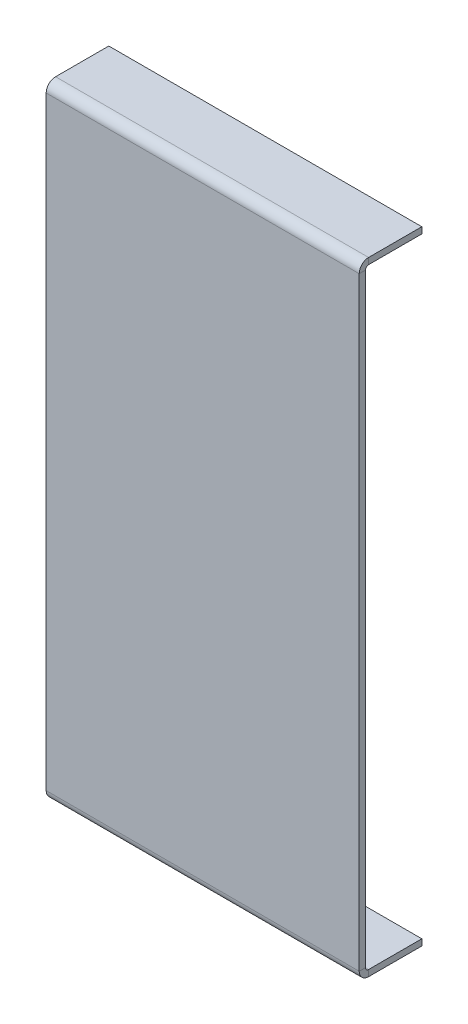
SolidWorks part; units mm, degrees
note: The reader was unsure of these and kept them because the rebuilt part matched: flange length of "边线-法兰1".
ref_plane "前视基准面" through (0, 0, 0) normal (0, 0, 1) x (1, 0, 0)
ref_plane "上视基准面" through (0, 0, 0) normal (0, 1, 0) x (1, 0, 0)
ref_plane "右视基准面" through (0, 0, 0) normal (1, 0, 0) x (0, 0, -1)
sketch "草图1" plane through (0, 0, 0) normal (0, 0, 1) x (1, 0, 0)
  line L1 (-50, 99.5) -> (50, 99.5)
  line L2 (-50, 99.5) -> (-50, -99.5)
  line L3 (-50, -99.5) -> (50, -99.5)
  line L4 (50, 99.5) -> (50, -99.5)
  line L5 (-50, 99.5) -> (50, -99.5) construction
  line L6 (-50, -99.5) -> (50, 99.5) construction
  point P0 (0, 0)
  dimension "D1" = 100
  dimension "D2" = 199
base flange "基体-法兰1" sketch "草图1" thickness 2 reverse thickness direction no parameters "D1"=1
edge flange "边线-法兰1" sketch "草图10" flange profiles "草图10", "草图11" flange angle 90 flange length 20 flange position material inside bend radius 1 thickness 2 relief rectangular parameters "D6"=10, "D8"=1
sketch "草图10" plane through (0, 99.5, -2) normal (0, -1, 0) x (-1, 0, 0)
  line L1 (50, 0) -> (-50, 0) construction
  line L2 (-50, 0) -> (-50, 18)
  line L3 (-50, 18) -> (50, 18)
  line L4 (50, 18) -> (50, 0)
  line L5 (50, 0) -> (-50, 0)
sketch "草图11" plane through (0, -99.5, -2) normal (0, 1, 0) x (1, 0, 0)
  line L0 (50, 0) -> (-50, 0) construction
  line L1 (50, 0) -> (-50, 0)
  line L2 (50, 0) -> (50, 18)
  line L3 (50, 18) -> (-50, 18)
  line L4 (-50, 18) -> (-50, 0)
bend "边线折弯1" bend radius 1 bend angle 90 parameters "D5"=1
bend "边线折弯2" bend radius 1 bend angle 90 parameters "D5"=2
sketch "折弯-线1" [suppressed] plane through (0, 0, 0) normal (0, 1, 0) x (1, 0, 0)
sketch "边界框1" [suppressed] plane through (0, 0, 0) normal (0, 1, 0) x (1, 0, 0)
sheet metal parameters "钣金6" thickness 2 parameters "D1"=1
flat pattern "平板型式6" [suppressed]
sketch "折弯-线2" plane through (0, 0, 0) normal (0, 1, 0) x (1, 0, 0)
sketch "边界框2" [suppressed] plane through (0, 0, 0) normal (0, 1, 0) x (1, 0, 0)
sheet metal parameters "钣金7" thickness 2 parameters "D1"=1
flat pattern "平板型式6"
sketch "折弯-线2" plane through (0, 0, 0) normal (0, 0, 1) x (1, 0, 0)
  line L0 (-50, -97.9) -> (50, -97.9) construction
  line L1 (50, 97.9) -> (-50, 97.9) construction
  line L2 (-50, -97.9) -> (50, -97.9) construction
  line L3 (50, 97.9) -> (-50, 97.9) construction
sketch3d "边界框2" [suppressed]
  line L0 (50, 116.3, 0) -> (50, -116.3, 0) construction
  line L1 (-50, 116.3, 0) -> (-50, -116.3, 0) construction
  line L2 (50, 116.3, 0) -> (-50, 116.3, 0) construction
  line L3 (50, -116.3, 0) -> (-50, -116.3, 0) construction
bend of the flat pattern "展开-<边线折弯1>1"
bend of the flat pattern "展开-<边线折弯2>1"
